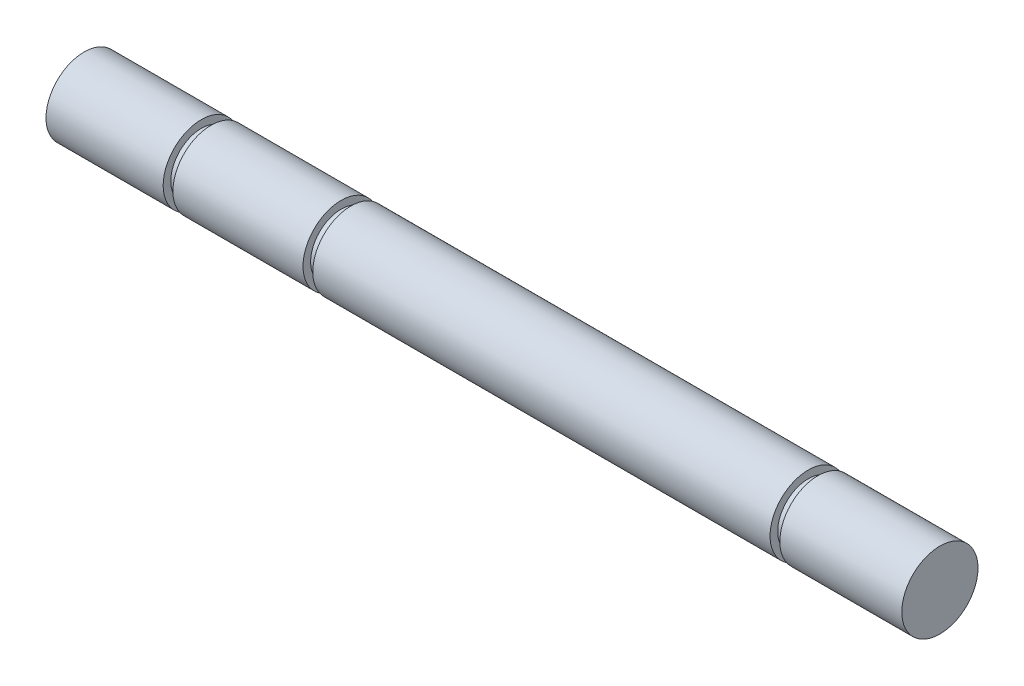
SolidWorks part; units mm, degrees
material "Plain Carbon Steel"
ref_plane "Front Plane" through (0, 0, 0) normal (0, 0, 1) x (1, 0, 0)
ref_plane "Top Plane" through (0, 0, 0) normal (0, 1, 0) x (1, 0, 0)
ref_plane "Right Plane" through (0, 0, 0) normal (1, 0, 0) x (0, 0, -1)
sketch "Sketch1" plane through (0, 0, 0) normal (1, 0, 0) x (0, 0, -1)
  circle A0 centre (0, 0) radius 2.5
  dimension "D1" = 5
extrude "Boss-Extrude1" add sketch "Sketch1" along normal blind 100
ref_plane "Plane1" through (92, 0, 0) normal (1, 0, 0) x (0, 0, -1)
sketch "Sketch2" plane through (92, 0, 0) normal (1, 0, 0) x (0, 0, -1)
  circle A0 centre (0, 0) radius 2
  circle A1 centre (0, 0) radius 2.5
  dimension "D1" = 4
  dimension "D2" = 5
extrude "Cut-Extrude1" cut sketch "Sketch2" against normal blind 0.64
ref_plane "Plane2" through (61.36, 0, 0) normal (1, 0, 0) x (0, 0, -1)
sketch "Sketch3" plane through (61.36, 0, 0) normal (1, 0, 0) x (0, 0, -1)
  circle A0 centre (0, 0) radius 2.5
  circle A1 centre (0, 0) radius 2
  dimension "D1" = 4
  dimension "D2" = 5
extrude "Cut-Extrude2" cut sketch "Sketch3" against normal blind 0.64
ref_plane "Plane3" through (43.86, 0, 0) normal (-1, 0, 0) x (0, 0, 1)
sketch "Sketch4" plane through (43.86, 0, 0) normal (-1, 0, 0) x (0, 0, 1)
  circle A0 centre (0, 0) radius 2.5
  dimension "D1" = 5
extrude "Cut-Extrude3" cut sketch "Sketch4" along normal up to surface (43.86 mm away) up to face at (0, 0, -2.5)
ref_plane "Plane4" through (52.185, 0, 0) normal (-1, 0, 0) x (0, 0, 1)
sketch "Sketch6" plane through (52.185, 0, 0) normal (-1, 0, 0) x (0, 0, 1)
  circle A0 centre (0, 0) radius 2
  circle A1 centre (0, 0) radius 2.5
  dimension "D1" = 5
  dimension "D2" = 4
extrude "Cut-Extrude4" cut sketch "Sketch6" along normal blind 0.64
